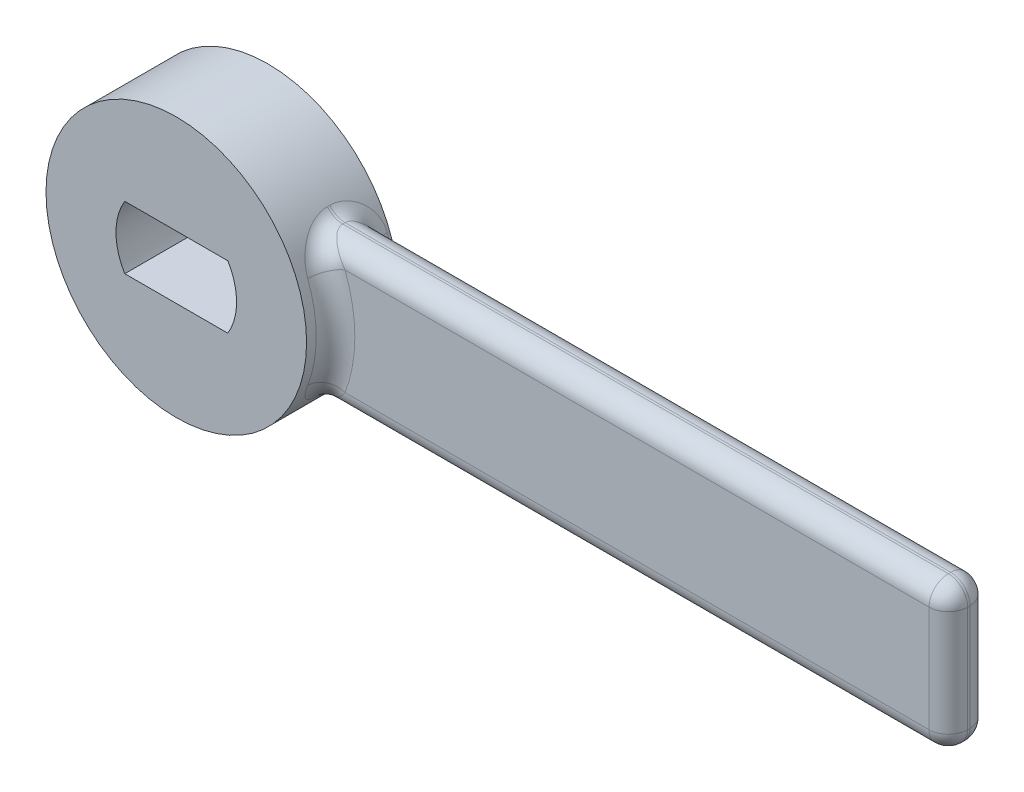
SolidWorks part; units mm, degrees
material "Простая углеродистая сталь"
ref_plane "Спереди" through (0, 0, 0) normal (0, 0, 1) x (1, 0, 0)
ref_plane "Сверху" through (0, 0, 0) normal (0, 1, 0) x (1, 0, 0)
ref_plane "Справа" through (0, 0, 0) normal (1, 0, 0) x (0, 0, -1)
sketch "Эскиз1" plane through (0, 0, 0) normal (0, 0, 1) x (1, 0, 0)
  line L0 (-10.6771, 6.5) -> (10.6771, 6.5)
  line L1 (0, 0) -> (27, 0) construction
  line L2 (-10.6771, -6.5) -> (10.6771, -6.5)
  circle A0 centre (0, 0) radius 27
  arc A1 (-10.6771, 6.5) -> (-10.6771, -6.5) centre (0, 0) ccw
  arc A2 (10.6771, 6.5) -> (10.6771, -6.5) centre (0, 0) cw
  dimension "D1" = 54
  dimension "D3" = 12.5
  dimension "D4" = 12.5
  dimension "D2" = 13
extrude "Бобышка-Вытянуть1" add sketch "Эскиз1" along normal blind 19
sketch "Эскиз2" plane through (0, 0, 0) normal (1, 0, 0) x (0, 0, -1)
  line L0 (-13, 15) -> (-13, -15)
  line L1 (-13, -15) -> (-4.5, -15)
  line L2 (-4.5, -15) -> (-4.5, 15)
  line L3 (-4.5, 15) -> (-13, 15)
  line L4 (0, -27) -> (0, 27) construction
  point P6 (-4.5, 0)
  dimension "D1" = 4.5
  dimension "D2" = 8.5
  dimension "D3" = 30
extrude "Бобышка-Вытянуть2" add sketch "Эскиз2" against normal up to surface (131.5501 mm away) from offset 154 up to face at (27, 0, 19)
fillet "Скругление1" radius 4 12 edges at (27, 0, 13) (88.225, 15, 13) (22.4499, 15, 8.75) (88.225, 15, 4.5) (27, 0, 4.5) (88.225, -15, 4.5) (22.4499, -15, 8.75) (88.225, -15, 13) (154, 0, 4.5) (154, -15, 8.75) (154, 0, 13) (154, 15, 8.75)
